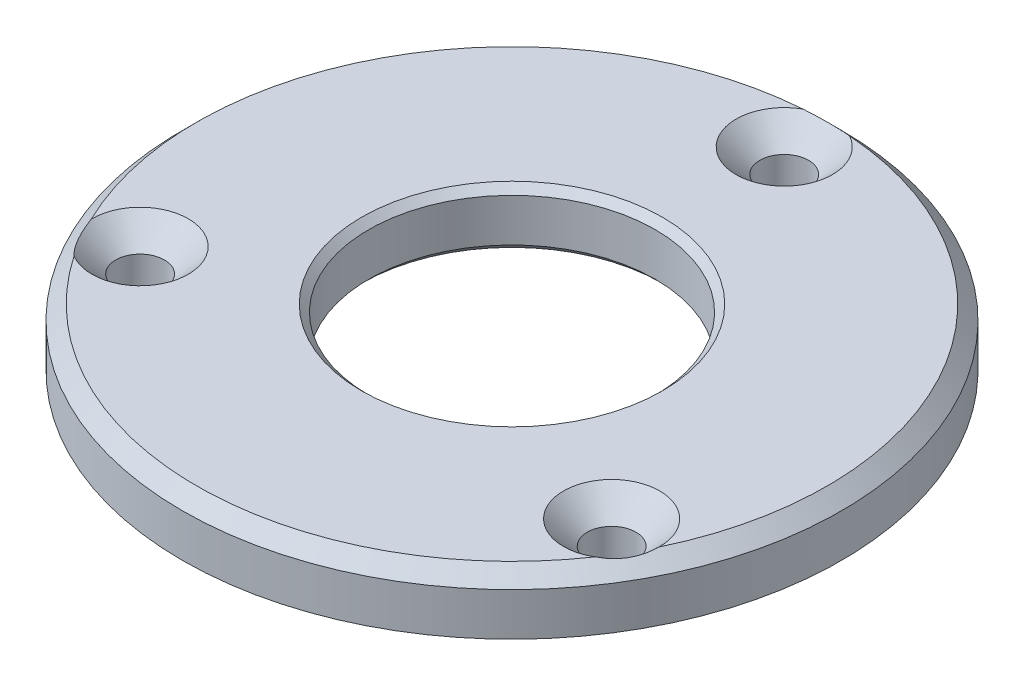
SolidWorks part; units mm, degrees
material "6061-T6 Aluminum"
ref_plane "Front Plane" through (0, 0, 0) normal (0, 0, 1) x (1, 0, 0)
ref_plane "Top Plane" through (0, 0, 0) normal (0, 1, 0) x (1, 0, 0)
ref_plane "Right Plane" through (0, 0, 0) normal (1, 0, 0) x (0, 0, -1)
sketch "Sketch1" plane through (0, 0, 0) normal (0, 1, 0) x (1, 0, 0)
  circle A0 centre (0, 0) radius 10
  circle A1 centre (0, 0) radius 23
  dimension "D1" = 20
  dimension "D2" = 46
extrude "Boss-Extrude1" add sketch "Sketch1" along normal blind 4
chamfer "Chamfer1" distance 0.5 angle 45 2 edges at (0, 0, 10) (0, 4, 10)
chamfer "Chamfer2" distance 1 angle 45 1 edges at (0, 4, 23)
sketch "Sketch2" plane through (0, 4, 0) normal (0, 1, 0) x (1, 0, 0)
  line L0 (0, 19) -> (-16.4545, -9.5) construction
  line L1 (-16.4545, -9.5) -> (16.4545, -9.5) construction
  line L2 (16.4545, -9.5) -> (0, 19) construction
  circle A0 centre (0, 0) radius 19 construction
  point P3 (0, 19)
  point P4 (-16.4545, -9.5)
  point P5 (16.4545, -9.5)
  dimension "D1" = 38
hole_wizard "CSK for M3 SFHCS1" positions "Sketch3" profile "Sketch4" countersink size "M3" standard "ANSI Metric" end condition through all
sketch "Sketch3" plane through (0, 4, 0) normal (0, 1, 0) x (1, 0, 0)
  point P0 (0, 19)
  point P3 (16.4545, -9.5)
  point P6 (-16.4545, -9.5)
sketch "Sketch4" plane through (0, 4, -19) normal (1, 0, 0) x (0, 0, 1)
  line L0 (0, 0) -> (0, 4)
  line L1 (0, 4) -> (1.7, 4)
  line L2 (1.7, 4) -> (1.7, 1.66)
  line L3 (1.7, 1.66) -> (3.36, 0)
  line L5 (3.36, 0) -> (0, 0)
  line L6 (-1.7, 1.66) -> (-3.36, 0) construction
  line L11 (0, -6.35) -> (0, 107.95) construction
  dimension "Thru Hole Dia." = 3.4
  dimension "Thru Hole Depth" = 4
  dimension "Near C'Sink Dia." = 6.72
  dimension "Near C'Sink Angle" = 90
